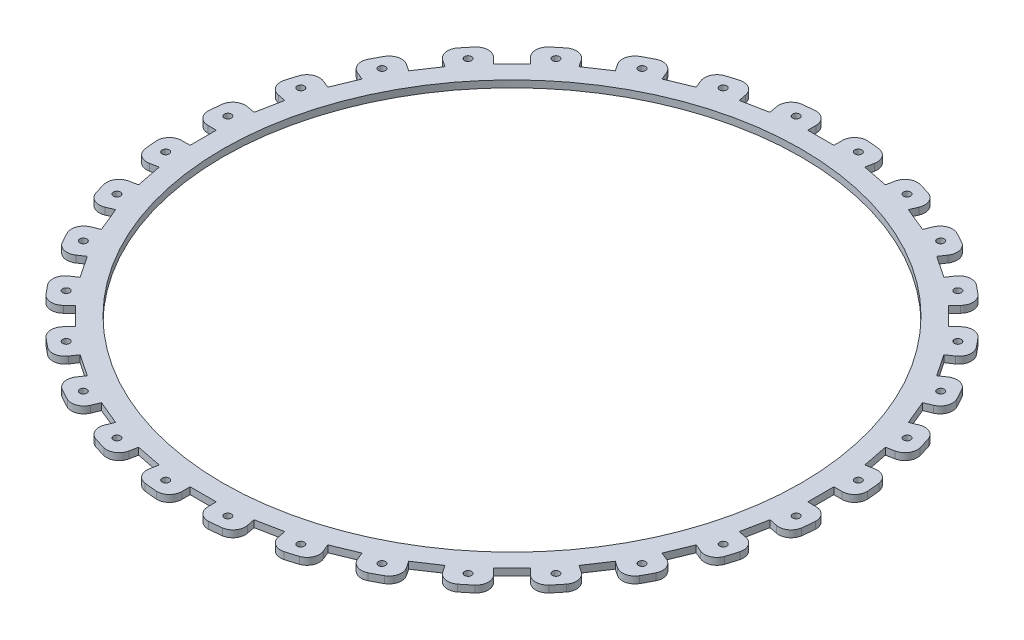
SolidWorks part; units mm, degrees
ref_plane "Front" through (0, 0, 0) normal (0, 0, 1) x (1, 0, 0)
ref_plane "Top" through (0, 0, 0) normal (0, 1, 0) x (1, 0, 0)
ref_plane "Right" through (0, 0, 0) normal (1, 0, 0) x (0, 0, -1)
sketch "Sketch1" plane through (0, 0, 0) normal (0, 1, 0) x (1, 0, 0)
  line L0 (133.35, 0) -> (142.367, 0) construction
  line L1 (152.0161, 6.0325) -> (142.367, 6.0325)
  line L2 (150.272, -23.7403) -> (140.8083, -21.8578)
  line L3 (152.0161, -6.0325) -> (142.367, -6.0325)
  line L4 (142.367, 6.0325) -> (142.367, -6.0325)
  line L5 (133.35, 0) -> (142.367, -6.0325) construction
  line L6 (133.35, 0) -> (142.367, 6.0325) construction
  line L7 (147.9182, -35.5735) -> (138.4546, -33.691)
  line L8 (140.8083, -21.8578) -> (138.4546, -33.691)
  line L9 (130.7877, -26.0153) -> (139.6315, -27.7744) construction
  line L10 (130.7877, -26.0153) -> (138.4546, -33.691) construction
  line L11 (130.7877, -26.0153) -> (140.8083, -21.8578) construction
  line L12 (142.7531, -52.6007) -> (133.8385, -48.9082)
  line L13 (138.136, -63.7473) -> (129.2214, -60.0548)
  line L14 (133.8385, -48.9082) -> (129.2214, -60.0548)
  line L15 (123.1993, -51.0308) -> (131.53, -54.4815) construction
  line L16 (123.1993, -51.0308) -> (129.2214, -60.0548) construction
  line L17 (123.1993, -51.0308) -> (133.8385, -48.9082) construction
  line L18 (129.7482, -79.4398) -> (121.7253, -74.079)
  line L19 (123.0453, -89.4714) -> (115.0224, -84.1107)
  line L20 (121.7253, -74.079) -> (115.0224, -84.1107)
  line L21 (110.8765, -74.0853) -> (118.3738, -79.0949) construction
  line L22 (110.8765, -74.0853) -> (115.0224, -84.1107) construction
  line L23 (110.8765, -74.0853) -> (121.7253, -74.079) construction
  line L24 (111.7572, -103.226) -> (104.9343, -96.403)
  line L25 (103.226, -111.7572) -> (96.403, -104.9343)
  line L26 (104.9343, -96.403) -> (96.403, -104.9343)
  line L27 (94.2927, -94.2927) -> (100.6687, -100.6687) construction
  line L28 (94.2927, -94.2927) -> (96.403, -104.9343) construction
  line L29 (94.2927, -94.2927) -> (104.9343, -96.403) construction
  line L30 (89.4714, -123.0453) -> (84.1107, -115.0224)
  line L31 (79.4398, -129.7482) -> (74.079, -121.7253)
  line L32 (84.1107, -115.0224) -> (74.079, -121.7253)
  line L33 (74.0853, -110.8765) -> (79.0949, -118.3738) construction
  line L34 (74.0853, -110.8765) -> (74.079, -121.7253) construction
  line L35 (74.0853, -110.8765) -> (84.1107, -115.0224) construction
  line L36 (63.7473, -138.136) -> (60.0548, -129.2214)
  line L37 (52.6007, -142.7531) -> (48.9082, -133.8385)
  line L38 (60.0548, -129.2214) -> (48.9082, -133.8385)
  line L39 (51.0308, -123.1993) -> (54.4815, -131.53) construction
  line L40 (51.0308, -123.1993) -> (48.9082, -133.8385) construction
  line L41 (51.0308, -123.1993) -> (60.0548, -129.2214) construction
  line L42 (35.5735, -147.9182) -> (33.691, -138.4546)
  line L43 (23.7403, -150.272) -> (21.8578, -140.8083)
  line L44 (33.691, -138.4546) -> (21.8578, -140.8083)
  line L45 (26.0153, -130.7877) -> (27.7744, -139.6315) construction
  line L46 (26.0153, -130.7877) -> (21.8578, -140.8083) construction
  line L47 (26.0153, -130.7877) -> (33.691, -138.4546) construction
  line L48 (6.0325, -152.0161) -> (6.0325, -142.367)
  line L49 (-6.0325, -152.0161) -> (-6.0325, -142.367)
  line L50 (6.0325, -142.367) -> (-6.0325, -142.367)
  line L51 (0, -133.35) -> (0, -142.367) construction
  line L52 (0, -133.35) -> (-6.0325, -142.367) construction
  line L53 (0, -133.35) -> (6.0325, -142.367) construction
  line L54 (-23.7403, -150.272) -> (-21.8578, -140.8083)
  line L55 (-35.5735, -147.9182) -> (-33.691, -138.4546)
  line L56 (-21.8578, -140.8083) -> (-33.691, -138.4546)
  line L57 (-26.0153, -130.7877) -> (-27.7744, -139.6315) construction
  line L58 (-26.0153, -130.7877) -> (-33.691, -138.4546) construction
  line L59 (-26.0153, -130.7877) -> (-21.8578, -140.8083) construction
  line L60 (-52.6007, -142.7531) -> (-48.9082, -133.8385)
  line L61 (-63.7473, -138.136) -> (-60.0548, -129.2214)
  line L62 (-48.9082, -133.8385) -> (-60.0548, -129.2214)
  line L63 (-51.0308, -123.1993) -> (-54.4815, -131.53) construction
  line L64 (-51.0308, -123.1993) -> (-60.0548, -129.2214) construction
  line L65 (-51.0308, -123.1993) -> (-48.9082, -133.8385) construction
  line L66 (-79.4398, -129.7482) -> (-74.079, -121.7253)
  line L67 (-89.4714, -123.0453) -> (-84.1107, -115.0224)
  line L68 (-74.079, -121.7253) -> (-84.1107, -115.0224)
  line L69 (-74.0853, -110.8765) -> (-79.0949, -118.3738) construction
  line L70 (-74.0853, -110.8765) -> (-84.1107, -115.0224) construction
  line L71 (-74.0853, -110.8765) -> (-74.079, -121.7253) construction
  line L72 (-103.226, -111.7572) -> (-96.403, -104.9343)
  line L73 (-111.7572, -103.226) -> (-104.9343, -96.403)
  line L74 (-96.403, -104.9343) -> (-104.9343, -96.403)
  line L75 (-94.2927, -94.2927) -> (-100.6687, -100.6687) construction
  line L76 (-94.2927, -94.2927) -> (-104.9343, -96.403) construction
  line L77 (-94.2927, -94.2927) -> (-96.403, -104.9343) construction
  line L78 (-123.0453, -89.4714) -> (-115.0224, -84.1107)
  line L79 (-129.7482, -79.4398) -> (-121.7253, -74.079)
  line L80 (-115.0224, -84.1107) -> (-121.7253, -74.079)
  line L81 (-110.8765, -74.0853) -> (-118.3738, -79.0949) construction
  line L82 (-110.8765, -74.0853) -> (-121.7253, -74.079) construction
  line L83 (-110.8765, -74.0853) -> (-115.0224, -84.1107) construction
  line L84 (-138.136, -63.7473) -> (-129.2214, -60.0548)
  line L85 (-142.7531, -52.6007) -> (-133.8385, -48.9082)
  line L86 (-129.2214, -60.0548) -> (-133.8385, -48.9082)
  line L87 (-123.1993, -51.0308) -> (-131.53, -54.4815) construction
  line L88 (-123.1993, -51.0308) -> (-133.8385, -48.9082) construction
  line L89 (-123.1993, -51.0308) -> (-129.2214, -60.0548) construction
  line L90 (-147.9182, -35.5735) -> (-138.4546, -33.691)
  line L91 (-150.272, -23.7403) -> (-140.8083, -21.8578)
  line L92 (-138.4546, -33.691) -> (-140.8083, -21.8578)
  line L93 (-130.7877, -26.0153) -> (-139.6315, -27.7744) construction
  line L94 (-130.7877, -26.0153) -> (-140.8083, -21.8578) construction
  line L95 (-130.7877, -26.0153) -> (-138.4546, -33.691) construction
  line L96 (-152.0161, -6.0325) -> (-142.367, -6.0325)
  line L97 (-152.0161, 6.0325) -> (-142.367, 6.0325)
  line L98 (-142.367, -6.0325) -> (-142.367, 6.0325)
  line L99 (-133.35, 0) -> (-142.367, 0) construction
  line L100 (-133.35, 0) -> (-142.367, 6.0325) construction
  line L101 (-133.35, 0) -> (-142.367, -6.0325) construction
  line L102 (-150.272, 23.7403) -> (-140.8083, 21.8578)
  line L103 (-147.9182, 35.5735) -> (-138.4546, 33.691)
  line L104 (-140.8083, 21.8578) -> (-138.4546, 33.691)
  line L105 (-130.7877, 26.0153) -> (-139.6315, 27.7744) construction
  line L106 (-130.7877, 26.0153) -> (-138.4546, 33.691) construction
  line L107 (-130.7877, 26.0153) -> (-140.8083, 21.8578) construction
  line L108 (-142.7531, 52.6007) -> (-133.8385, 48.9082)
  line L109 (-138.136, 63.7473) -> (-129.2214, 60.0548)
  line L110 (-133.8385, 48.9082) -> (-129.2214, 60.0548)
  line L111 (-123.1993, 51.0308) -> (-131.53, 54.4815) construction
  line L112 (-123.1993, 51.0308) -> (-129.2214, 60.0548) construction
  line L113 (-123.1993, 51.0308) -> (-133.8385, 48.9082) construction
  line L114 (-129.7482, 79.4398) -> (-121.7253, 74.079)
  line L115 (-123.0453, 89.4714) -> (-115.0224, 84.1107)
  line L116 (-121.7253, 74.079) -> (-115.0224, 84.1107)
  line L117 (-110.8765, 74.0853) -> (-118.3738, 79.0949) construction
  line L118 (-110.8765, 74.0853) -> (-115.0224, 84.1107) construction
  line L119 (-110.8765, 74.0853) -> (-121.7253, 74.079) construction
  line L120 (-111.7572, 103.226) -> (-104.9343, 96.403)
  line L121 (-103.226, 111.7572) -> (-96.403, 104.9343)
  line L122 (-104.9343, 96.403) -> (-96.403, 104.9343)
  line L123 (-94.2927, 94.2927) -> (-100.6687, 100.6687) construction
  line L124 (-94.2927, 94.2927) -> (-96.403, 104.9343) construction
  line L125 (-94.2927, 94.2927) -> (-104.9343, 96.403) construction
  line L126 (-89.4714, 123.0453) -> (-84.1107, 115.0224)
  line L127 (-79.4398, 129.7482) -> (-74.079, 121.7253)
  line L128 (-84.1107, 115.0224) -> (-74.079, 121.7253)
  line L129 (-74.0853, 110.8765) -> (-79.0949, 118.3738) construction
  line L130 (-74.0853, 110.8765) -> (-74.079, 121.7253) construction
  line L131 (-74.0853, 110.8765) -> (-84.1107, 115.0224) construction
  line L132 (-63.7473, 138.136) -> (-60.0548, 129.2214)
  line L133 (-52.6007, 142.7531) -> (-48.9082, 133.8385)
  line L134 (-60.0548, 129.2214) -> (-48.9082, 133.8385)
  line L135 (-51.0308, 123.1993) -> (-54.4815, 131.53) construction
  line L136 (-51.0308, 123.1993) -> (-48.9082, 133.8385) construction
  line L137 (-51.0308, 123.1993) -> (-60.0548, 129.2214) construction
  line L138 (-35.5735, 147.9182) -> (-33.691, 138.4546)
  line L139 (-23.7403, 150.272) -> (-21.8578, 140.8083)
  line L140 (-33.691, 138.4546) -> (-21.8578, 140.8083)
  line L141 (-26.0153, 130.7877) -> (-27.7744, 139.6315) construction
  line L142 (-26.0153, 130.7877) -> (-21.8578, 140.8083) construction
  line L143 (-26.0153, 130.7877) -> (-33.691, 138.4546) construction
  line L144 (-6.0325, 152.0161) -> (-6.0325, 142.367)
  line L145 (6.0325, 152.0161) -> (6.0325, 142.367)
  line L146 (-6.0325, 142.367) -> (6.0325, 142.367)
  line L147 (0, 133.35) -> (0, 142.367) construction
  line L148 (0, 133.35) -> (6.0325, 142.367) construction
  line L149 (0, 133.35) -> (-6.0325, 142.367) construction
  line L150 (23.7403, 150.272) -> (21.8578, 140.8083)
  line L151 (35.5735, 147.9182) -> (33.691, 138.4546)
  line L152 (21.8578, 140.8083) -> (33.691, 138.4546)
  line L153 (26.0153, 130.7877) -> (27.7744, 139.6315) construction
  line L154 (26.0153, 130.7877) -> (33.691, 138.4546) construction
  line L155 (26.0153, 130.7877) -> (21.8578, 140.8083) construction
  line L156 (52.6007, 142.7531) -> (48.9082, 133.8385)
  line L157 (63.7473, 138.136) -> (60.0548, 129.2214)
  line L158 (48.9082, 133.8385) -> (60.0548, 129.2214)
  line L159 (51.0308, 123.1993) -> (54.4815, 131.53) construction
  line L160 (51.0308, 123.1993) -> (60.0548, 129.2214) construction
  line L161 (51.0308, 123.1993) -> (48.9082, 133.8385) construction
  line L162 (79.4398, 129.7482) -> (74.079, 121.7253)
  line L163 (89.4714, 123.0453) -> (84.1107, 115.0224)
  line L164 (74.079, 121.7253) -> (84.1107, 115.0224)
  line L165 (74.0853, 110.8765) -> (79.0949, 118.3738) construction
  line L166 (74.0853, 110.8765) -> (84.1107, 115.0224) construction
  line L167 (74.0853, 110.8765) -> (74.079, 121.7253) construction
  line L168 (103.226, 111.7572) -> (96.403, 104.9343)
  line L169 (111.7572, 103.226) -> (104.9343, 96.403)
  line L170 (96.403, 104.9343) -> (104.9343, 96.403)
  line L171 (94.2927, 94.2927) -> (100.6687, 100.6687) construction
  line L172 (94.2927, 94.2927) -> (104.9343, 96.403) construction
  line L173 (94.2927, 94.2927) -> (96.403, 104.9343) construction
  line L174 (123.0453, 89.4714) -> (115.0224, 84.1107)
  line L175 (129.7482, 79.4398) -> (121.7253, 74.079)
  line L176 (115.0224, 84.1107) -> (121.7253, 74.079)
  line L177 (110.8765, 74.0853) -> (118.3738, 79.0949) construction
  line L178 (110.8765, 74.0853) -> (121.7253, 74.079) construction
  line L179 (110.8765, 74.0853) -> (115.0224, 84.1107) construction
  line L180 (138.136, 63.7473) -> (129.2214, 60.0548)
  line L181 (142.7531, 52.6007) -> (133.8385, 48.9082)
  line L182 (129.2214, 60.0548) -> (133.8385, 48.9082)
  line L183 (123.1993, 51.0308) -> (131.53, 54.4815) construction
  line L184 (123.1993, 51.0308) -> (133.8385, 48.9082) construction
  line L185 (123.1993, 51.0308) -> (129.2214, 60.0548) construction
  line L186 (147.9182, 35.5735) -> (138.4546, 33.691)
  line L187 (150.272, 23.7403) -> (140.8083, 21.8578)
  line L188 (138.4546, 33.691) -> (140.8083, 21.8578)
  line L189 (130.7877, 26.0153) -> (139.6315, 27.7744) construction
  line L190 (130.7877, 26.0153) -> (140.8083, 21.8578) construction
  line L191 (130.7877, 26.0153) -> (138.4546, 33.691) construction
  arc A0 (152.2699, 6.297) -> (152.2699, -6.297) centre (0, 0) ccw
  circle A1 centre (0, 0) radius 133.35
  arc A2 (152.0161, 6.0325) -> (152.2699, 6.297) centre (152.0161, 6.2865) ccw
  arc A3 (152.0161, -6.0325) -> (152.2699, -6.297) centre (152.0161, -6.2865) cw
  arc A4 (150.272, -23.7403) -> (150.5725, -23.5304) centre (150.3216, -23.4912) ccw
  arc A5 (147.9182, -35.5735) -> (148.1155, -35.8824) centre (147.8687, -35.8226) cw
  arc A6 (142.7531, -52.6007) -> (143.0888, -52.4535) centre (142.8503, -52.3661) ccw
  arc A7 (138.136, -63.7473) -> (138.2692, -64.0888) centre (138.0388, -63.982) cw
  arc A8 (129.7482, -79.4398) -> (130.1062, -79.3608) centre (129.8893, -79.2286) ccw
  arc A9 (123.0453, -89.4714) -> (123.1093, -89.8324) centre (122.9041, -89.6826) cw
  arc A10 (111.7572, -103.226) -> (112.1237, -103.2184) centre (111.9368, -103.0464) ccw
  arc A11 (103.226, -111.7572) -> (103.2184, -112.1237) centre (103.0464, -111.9368) cw
  arc A12 (89.4714, -123.0453) -> (89.8324, -123.1093) centre (89.6826, -122.9041) ccw
  arc A13 (79.4398, -129.7482) -> (79.3608, -130.1062) centre (79.2286, -129.8893) cw
  arc A14 (63.7473, -138.136) -> (64.0888, -138.2692) centre (63.982, -138.0388) ccw
  arc A15 (52.6007, -142.7531) -> (52.4535, -143.0888) centre (52.3661, -142.8503) cw
  arc A16 (35.5735, -147.9182) -> (35.8824, -148.1155) centre (35.8226, -147.8687) ccw
  arc A17 (23.7403, -150.272) -> (23.5304, -150.5725) centre (23.4912, -150.3216) cw
  arc A18 (6.0325, -152.0161) -> (6.297, -152.2699) centre (6.2865, -152.0161) ccw
  arc A19 (-6.0325, -152.0161) -> (-6.297, -152.2699) centre (-6.2865, -152.0161) cw
  arc A20 (-23.7403, -150.272) -> (-23.5304, -150.5725) centre (-23.4912, -150.3216) ccw
  arc A21 (-35.5735, -147.9182) -> (-35.8824, -148.1155) centre (-35.8226, -147.8687) cw
  arc A22 (-52.6007, -142.7531) -> (-52.4535, -143.0888) centre (-52.3661, -142.8503) ccw
  arc A23 (-63.7473, -138.136) -> (-64.0888, -138.2692) centre (-63.982, -138.0388) cw
  arc A24 (-79.4398, -129.7482) -> (-79.3608, -130.1062) centre (-79.2286, -129.8893) ccw
  arc A25 (-89.4714, -123.0453) -> (-89.8324, -123.1093) centre (-89.6826, -122.9041) cw
  arc A26 (-103.226, -111.7572) -> (-103.2184, -112.1237) centre (-103.0464, -111.9368) ccw
  arc A27 (-111.7572, -103.226) -> (-112.1237, -103.2184) centre (-111.9368, -103.0464) cw
  arc A28 (-123.0453, -89.4714) -> (-123.1093, -89.8324) centre (-122.9041, -89.6826) ccw
  arc A29 (-129.7482, -79.4398) -> (-130.1062, -79.3608) centre (-129.8893, -79.2286) cw
  arc A30 (-138.136, -63.7473) -> (-138.2692, -64.0888) centre (-138.0388, -63.982) ccw
  arc A31 (-142.7531, -52.6007) -> (-143.0888, -52.4535) centre (-142.8503, -52.3661) cw
  arc A32 (-147.9182, -35.5735) -> (-148.1155, -35.8824) centre (-147.8687, -35.8226) ccw
  arc A33 (-150.272, -23.7403) -> (-150.5725, -23.5304) centre (-150.3216, -23.4912) cw
  arc A34 (-152.0161, -6.0325) -> (-152.2699, -6.297) centre (-152.0161, -6.2865) ccw
  arc A35 (-152.0161, 6.0325) -> (-152.2699, 6.297) centre (-152.0161, 6.2865) cw
  arc A36 (-150.272, 23.7403) -> (-150.5725, 23.5304) centre (-150.3216, 23.4912) ccw
  arc A37 (-147.9182, 35.5735) -> (-148.1155, 35.8824) centre (-147.8687, 35.8226) cw
  arc A38 (-142.7531, 52.6007) -> (-143.0888, 52.4535) centre (-142.8503, 52.3661) ccw
  arc A39 (-138.136, 63.7473) -> (-138.2692, 64.0888) centre (-138.0388, 63.982) cw
  arc A40 (-129.7482, 79.4398) -> (-130.1062, 79.3608) centre (-129.8893, 79.2286) ccw
  arc A41 (-123.0453, 89.4714) -> (-123.1093, 89.8324) centre (-122.9041, 89.6826) cw
  arc A42 (-111.7572, 103.226) -> (-112.1237, 103.2184) centre (-111.9368, 103.0464) ccw
  arc A43 (-103.226, 111.7572) -> (-103.2184, 112.1237) centre (-103.0464, 111.9368) cw
  arc A44 (-89.4714, 123.0453) -> (-89.8324, 123.1093) centre (-89.6826, 122.9041) ccw
  arc A45 (-79.4398, 129.7482) -> (-79.3608, 130.1062) centre (-79.2286, 129.8893) cw
  arc A46 (-63.7473, 138.136) -> (-64.0888, 138.2692) centre (-63.982, 138.0388) ccw
  arc A47 (-52.6007, 142.7531) -> (-52.4535, 143.0888) centre (-52.3661, 142.8503) cw
  arc A48 (-35.5735, 147.9182) -> (-35.8824, 148.1155) centre (-35.8226, 147.8687) ccw
  arc A49 (-23.7403, 150.272) -> (-23.5304, 150.5725) centre (-23.4912, 150.3216) cw
  arc A50 (-6.0325, 152.0161) -> (-6.297, 152.2699) centre (-6.2865, 152.0161) ccw
  arc A51 (6.0325, 152.0161) -> (6.297, 152.2699) centre (6.2865, 152.0161) cw
  arc A52 (23.7403, 150.272) -> (23.5304, 150.5725) centre (23.4912, 150.3216) ccw
  arc A53 (35.5735, 147.9182) -> (35.8824, 148.1155) centre (35.8226, 147.8687) cw
  arc A54 (52.6007, 142.7531) -> (52.4535, 143.0888) centre (52.3661, 142.8503) ccw
  arc A55 (63.7473, 138.136) -> (64.0888, 138.2692) centre (63.982, 138.0388) cw
  arc A56 (79.4398, 129.7482) -> (79.3608, 130.1062) centre (79.2286, 129.8893) ccw
  arc A57 (89.4714, 123.0453) -> (89.8324, 123.1093) centre (89.6826, 122.9041) cw
  arc A58 (103.226, 111.7572) -> (103.2184, 112.1237) centre (103.0464, 111.9368) ccw
  arc A59 (111.7572, 103.226) -> (112.1237, 103.2184) centre (111.9368, 103.0464) cw
  arc A60 (123.0453, 89.4714) -> (123.1093, 89.8324) centre (122.9041, 89.6826) ccw
  arc A61 (129.7482, 79.4398) -> (130.1062, 79.3608) centre (129.8893, 79.2286) cw
  arc A62 (138.136, 63.7473) -> (138.2692, 64.0888) centre (138.0388, 63.982) ccw
  arc A63 (142.7531, 52.6007) -> (143.0888, 52.4535) centre (142.8503, 52.3661) cw
  arc A64 (147.9182, 35.5735) -> (148.1155, 35.8824) centre (147.8687, 35.8226) ccw
  arc A65 (150.272, 23.7403) -> (150.5725, 23.5304) centre (150.3216, 23.4912) cw
  point P4 (133.35, 0)
  point P231 (0, 0)
  point P328 (0, 0)
  dimension "D1" = 304.8
  dimension "D2" = 19.05
  dimension "D3" = 12.065
  dimension "D5" = 0.254
  dimension "D4" = 9.017
extrude "Boss-Extrude1" add sketch "Sketch1" along normal blind 3.175 contours A0 A1 region at (147.1915, 0, -10.3393)
sketch "Sketch3" plane through (0, 3.175, 0) normal (0, 1, 0) x (1, 0, 0)
  line L0 (-103.226, 111.7572) -> (-96.403, 104.9343) construction
  line L1 (-208.9745, 20.5822) -> (-53.4385, 5.2632) construction
  line L2 (-89.4714, 123.0453) -> (-84.1107, 115.0224) construction
  line L3 (-111.7572, -103.226) -> (-104.9343, -96.403) construction
  line L4 (-123.0453, -89.4714) -> (-115.0224, -84.1107) construction
  arc A0 (-79.0253, 107.4115) -> (-98.4618, -89.9305) centre (-208.9745, 20.5822) cw
  arc A1 (-89.9305, 98.4618) -> (-107.4115, -79.0253) centre (-171.2273, 16.8644) cw
  arc A2 (-89.9305, 98.4618) -> (-79.0253, 107.4115) centre (0, 0) cw
  arc A3 (-107.4115, -79.0253) -> (-98.4618, -89.9305) centre (0, 0) ccw
  circle A6 centre (0, 0) radius 133.35 construction
  point P13 (-56.5982, 5.5744)
  dimension "D1" = 3.175
extrude "Boss-Extrude3" [suppressed] add sketch "Sketch3" against normal up to surface (3.175 mm away) up to face at (0, 0, 0)
fillet "Fillet1" [suppressed] radius 6.35
sketch "Sketch5" plane through (0, 0, 0) normal (0, -1, 0) x (1, 0, 0)
  line L0 (0, 0) -> (151.6662, 14.9378) construction
  line L1 (-117.8068, 96.6815) -> (0, 0) construction
  line L2 (-123.0453, 89.4714) -> (-115.0224, 84.1107) construction
  line L3 (-115.0224, 84.1107) -> (-121.7253, 74.079) construction
  line L4 (-111.9442, 103.413) -> (-107.6284, 99.0971)
  line L5 (-123.2652, 89.6184) -> (-118.1903, 86.2274)
  arc A0 (152.2699, 6.297) -> (150.5725, 23.5304) centre (0, 0) ccw construction
  circle A1 centre (145.3467, 14.3154) radius 1.6383
  circle A2 centre (0, 0) radius 146.05 construction
  arc A3 (-112.1237, 103.2184) -> (-123.1093, 89.8324) centre (0, 0) ccw construction
  circle A4 centre (-112.8982, 92.6531) radius 1.6383
  arc A5 (-118.1903, 86.2274) -> (-119.4018, 94.7047) centre (-114.9951, 91.0093) cw
  arc A6 (-119.4018, 94.7047) -> (-123.2652, 89.6184) centre (0, 0) ccw
  arc A7 (-116.1791, 98.6316) -> (-111.9442, 103.413) centre (0, 0) cw
  arc A8 (-107.6284, 99.0971) -> (-116.1791, 98.6316) centre (-111.695, 95.0305) ccw
  dimension "D1" = 292.1
  dimension "D2" = 3.2766
  dimension "D3" = 3.2766
  dimension "D4" = 3.81
  dimension "D5" = 2.54
extrude "Cut-Extrude1" cut sketch "Sketch5" against normal through all contours A4 region at (-112.8982, 0, 92.6531)
ref_axis "Axis1" through (0, 50, 0) along (0, -1, 0)
pattern_circular "CirPattern1" [suppressed] count 16 over 360 about axis through (0, 50, 0) along (0, -1, 0) of bodies 105
extrude "Cut-Extrude2" cut sketch "Sketch5<3>" against normal through all contours A5 A6 L5 | A8 L4 A7 region at (-111.9152, 0, 101.4078) region at (-121.2929, 0, 89.9811)
sketch "Sketch5<3>" plane through (0, 0, 0) normal (0, -1, 0) x (1, 0, 0) same geometry as "Sketch5"
pattern_circular "CirPattern2" count 32 over 360 about axis through (0, 50, 0) along (0, -1, 0) of "Cut-Extrude2", "Cut-Extrude1"
